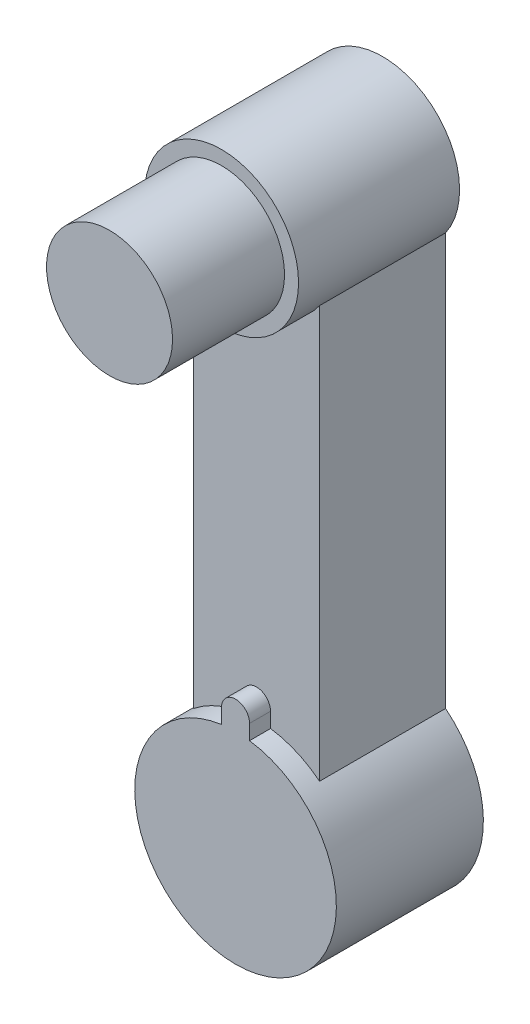
SolidWorks part; units mm, degrees
ref_plane "Front Plane" through (0, 0, 0) normal (0, 0, 1) x (1, 0, 0)
ref_plane "Top Plane" through (0, 0, 0) normal (0, 1, 0) x (1, 0, 0)
ref_plane "Right Plane" through (0, 0, 0) normal (1, 0, 0) x (0, 0, -1)
sketch "Sketch11" plane through (0, 0, 0) normal (0, 0, 1) x (1, 0, 0)
  line L1 (45, 56.205) -> (45, 350.3772)
  line L4 (-45, 56.205) -> (-45, 350.3772)
  circle A0 centre (0, 0) radius 72
  circle A1 centre (0, 382) radius 55
extrude "Boss-Extrude5" add sketch "Sketch11" along normal blind 90 contours A1 L4 A0 L1 region at (0, 200.5283, 0)
extrude "Boss-Extrude6" add sketch "Sketch11<3>" along normal blind 115 contours A1 region at (0, 382, 0)
sketch "Sketch11<3>" plane through (0, 0, 0) normal (0, 0, 1) x (1, 0, 0) same geometry as "Sketch11"
extrude "Boss-Extrude7" add sketch "Sketch11<4>" along normal blind 105 contours A0 region at (0, 0, 0)
sketch "Sketch11<4>" plane through (0, 0, 0) normal (0, 0, 1) x (1, 0, 0) same geometry as "Sketch11"
sketch "Sketch13" plane through (0, 0, 90) normal (0, 0, 1) x (1, 0, 0)
  line L2 (10, 82) -> (10, 71.3022)
  line L3 (10, 71.3022) -> (-10, 71.3022)
  line L4 (-10, 82) -> (-10, 71.3022)
  arc A1 (10, 82) -> (-10, 82) centre (0, 82) ccw
  arc A2 (45, 56.205) -> (-45, 56.205) centre (0, 0) ccw construction
extrude "Boss-Extrude8" add sketch "Sketch13" along normal blind 15
sketch "Sketch17" plane through (0, 0, 115) normal (0, 0, 1) x (1, 0, 0)
  circle A0 centre (0, 382) radius 45
extrude "Boss-Extrude9" add sketch "Sketch17" along normal blind 80
sketch "Sketch24" plane through (0, 0, 0) normal (0, 0, -1) x (-1, 0, 0)
  circle A0 centre (0, 382) radius 53
